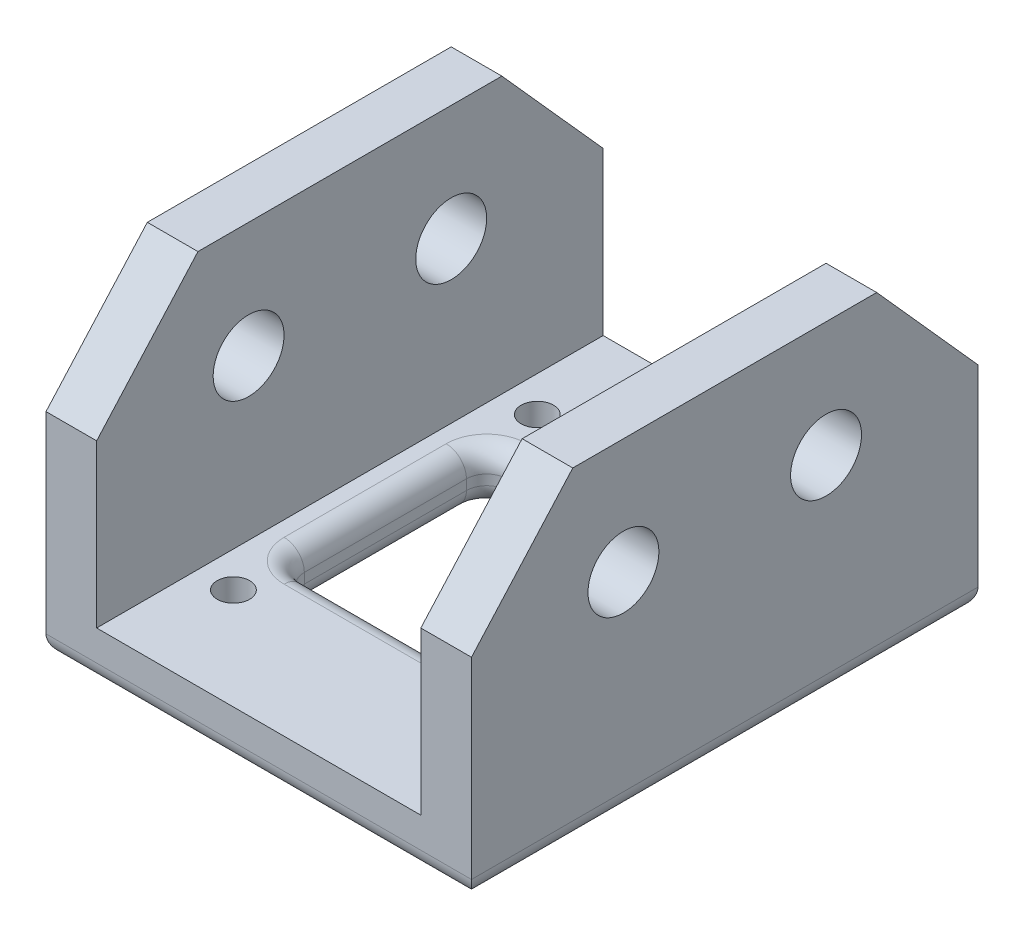
SolidWorks part; units mm, degrees
ref_plane "Front Plane" through (0, 0, 0) normal (0, 0, 1) x (1, 0, 0)
ref_plane "Top Plane" through (0, 0, 0) normal (0, 1, 0) x (1, 0, 0)
ref_plane "Right Plane" through (0, 0, 0) normal (1, 0, 0) x (0, 0, -1)
ref_plane "MiddlePlane" through (-26.67, 0, 0) normal (1, 0, 0) x (0, 0, -1)
sketch "Sketch1" plane through (0, 0, 0) normal (1, 0, 0) x (0, 0, -1)
  line L1 (0, 0) -> (63.5, 0)
  line L2 (0, 0) -> (0, 6.35)
  line L3 (0, 6.35) -> (63.5, 6.35)
  line L4 (63.5, 0) -> (63.5, 6.35)
  dimension "D1" = 6.35
  dimension "D2" = 63.5
extrude "Boss-Extrude1" add sketch "Sketch1" against normal blind 53.34
sketch "Sketch2" plane through (0, 0, 0) normal (1, 0, 0) x (0, 0, -1)
  line L0 (0, 6.35) -> (0, 26.67)
  line L1 (0, 26.67) -> (12.7, 40.869)
  line L2 (12.7, 40.869) -> (50.8, 40.869)
  line L3 (50.8, 40.869) -> (63.5, 26.67)
  line L4 (63.5, 26.67) -> (63.5, 6.35)
  line L5 (63.5, 6.35) -> (0, 6.35)
  point P7 (31.75, 40.869)
  point P10 (31.75, 6.35)
  dimension "D1" = 38.1
  dimension "D2" = 20.32
  dimension "D4" = 19.05
  dimension "D5" = 19.05
extrude "Boss-Extrude2" add sketch "Sketch2" against normal blind 6.35
sketch "Sketch11" plane through (0, 0, 0) normal (1, 0, 0) x (0, 0, -1)
  line L3 (50.8, 40.869) -> (12.7, 40.869) construction
  line L4 (0, 26.67) -> (0, 0) construction
  line L5 (63.5, 0) -> (63.5, 26.67) construction
  circle A4 centre (19.05, 26.391) radius 4.445
  circle A5 centre (44.45, 26.391) radius 4.445
  dimension "D1" = 8.89
  dimension "D3" = 19.05
  dimension "D4" = 19.05
  dimension "D2" = 14.478
extrude "Cut-Extrude1" cut sketch "Sketch11" against normal up to next
ref_plane "Plane2" through (0, 33.02, 0) normal (0, -1, 0) x (-1, 0, 0)
fillet "Fillet1" radius 2.54 4 edges at (0, 0, -31.75) (-26.67, 0, -63.5) (-53.34, 0, -31.75) (-26.67, 0, 0)
sketch "Sketch19" plane through (0, 0, 0) normal (0, -1, 0) x (1, 0, 0)
  line L0 (-26.67, -63.5) -> (-26.67, 0) construction
  line L1 (0, -63.5) -> (-53.34, -63.5) construction
  line L2 (-53.34, 0) -> (0, 0) construction
  line L3 (0, -31.75) -> (-53.34, -31.75) construction
  line L4 (0, 0) -> (0, -63.5) construction
  line L5 (-53.34, -63.5) -> (-53.34, 0) construction
  line L7 (-10.795, -50.8) -> (-42.545, -50.8) construction
  line L8 (-10.795, -50.8) -> (-10.795, -12.7) construction
  line L9 (-10.795, -12.7) -> (-42.545, -12.7) construction
  line L10 (-42.545, -50.8) -> (-42.545, -12.7) construction
  line L11 (-10.795, -50.8) -> (-42.545, -12.7) construction
  line L12 (-10.795, -12.7) -> (-42.545, -50.8) construction
  circle A0 centre (-10.795, -50.8) radius 2.032
  circle A1 centre (-42.545, -50.8) radius 2.032
  circle A2 centre (-42.545, -12.7) radius 2.032
  circle A3 centre (-10.795, -12.7) radius 2.032
  point P12 (-26.67, -31.75)
  dimension "D3" = 4.064
  dimension "D1" = 31.75
  dimension "D2" = 38.1
extrude "Cut-Extrude2" cut sketch "Sketch19" against normal up to next
mirror "Mirror1" about plane through (-26.67, 0, 0) normal (1, 0, 0) of "Cut-Extrude1", "Boss-Extrude2"
sketch "Sketch20" plane through (0, 0, 0) normal (0, -1, 0) x (1, 0, 0)
  line L0 (-2.54, -60.96) -> (-2.54, -2.54) construction
  line L1 (-13.335, -19.05) -> (-40.005, -19.05)
  line L2 (-10.795, -21.59) -> (-10.795, -41.91)
  line L3 (-13.335, -44.45) -> (-40.005, -44.45)
  line L4 (-42.545, -21.59) -> (-42.545, -41.91)
  line L5 (-50.8, -60.96) -> (-2.54, -60.96) construction
  arc A0 (-40.005, -44.45) -> (-42.545, -41.91) centre (-40.005, -41.91) cw
  arc A1 (-10.795, -41.91) -> (-13.335, -44.45) centre (-13.335, -41.91) cw
  arc A2 (-13.335, -19.05) -> (-10.795, -21.59) centre (-13.335, -21.59) cw
  arc A3 (-40.005, -19.05) -> (-42.545, -21.59) centre (-40.005, -21.59) ccw
  point P4 (-10.795, -31.75)
  point P7 (-2.54, -31.75)
  point P8 (-26.67, -44.45)
  point P11 (-26.67, -60.96)
  point P14 (-42.545, -44.45)
  point P17 (-10.795, -44.45)
  point P22 (-42.545, -19.05)
  dimension "D3" = 2.54
  dimension "D1" = 25.4
  dimension "D2" = 31.75
extrude "Cut-Extrude3" cut sketch "Sketch20" against normal up to surface (6.35 mm away) up to face at (-26.67, 6.35, -31.75)
fillet "Fillet2" radius 2.54 16 edges at (-11.5389, 6.35, -43.7061) (-26.67, 6.35, -44.45) (-41.8011, 6.35, -43.7061) (-42.545, 6.35, -31.75) (-41.8011, 6.35, -19.7939) (-26.67, 6.35, -19.05) (-11.5389, 6.35, -19.7939) (-11.5389, 0, -43.7061) (-11.5389, 0, -19.7939) (-26.67, 0, -19.05) (-41.8011, 0, -19.7939) (-42.545, 0, -31.75) (-41.8011, 0, -43.7061) (-26.67, 0, -44.45) (-10.795, 6.35, -31.75) (-10.795, 0, -31.75)
